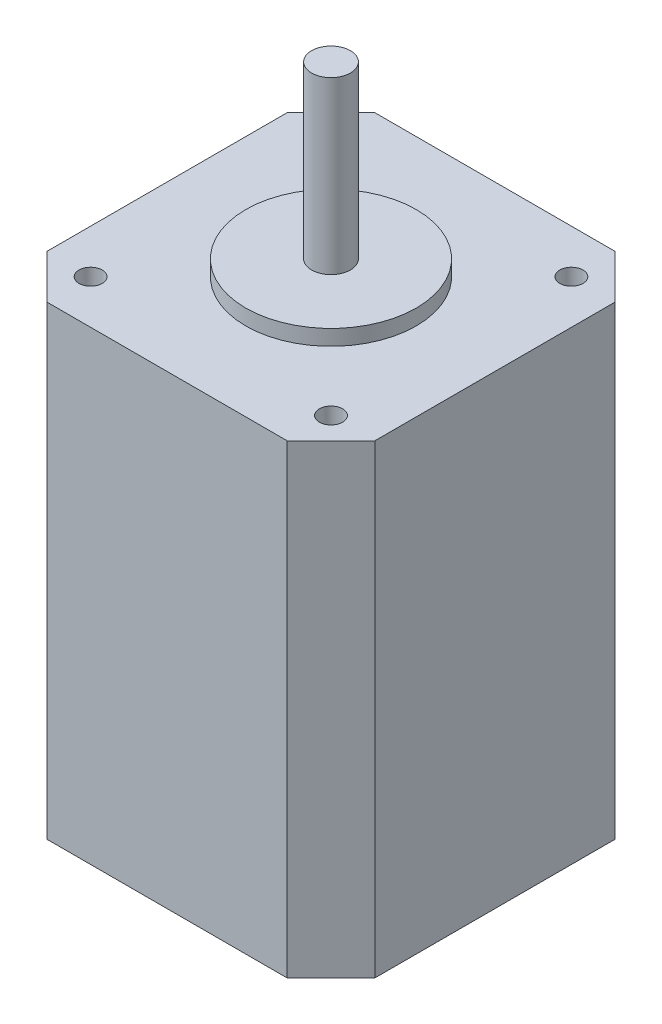
SolidWorks part; units mm, degrees
ref_plane "前基準面" through (0, 0, 0) normal (0, 0, 1) x (1, 0, 0)
ref_plane "上基準面" through (0, 0, 0) normal (0, 1, 0) x (1, 0, 0)
ref_plane "右基準面" through (0, 0, 0) normal (1, 0, 0) x (0, 0, -1)
sketch "草圖1" plane through (0, 0, 0) normal (0, 1, 0) x (1, 0, 0)
  line L0 (-15.5, -21.15) -> (-15.5, 21.15) construction
  line L1 (-15.5, 21.15) -> (15.5, 21.15)
  line L2 (-21.15, 15.5) -> (-21.15, -15.5)
  line L3 (-15.5, -21.15) -> (15.5, -21.15)
  line L4 (21.15, 15.5) -> (21.15, -15.5)
  line L5 (0, -21.15) -> (0, 21.15) construction
  line L6 (-21.15, 0) -> (21.15, 0) construction
  line L7 (15.5, -21.15) -> (15.5, 21.15) construction
  line L8 (-21.15, 15.5) -> (21.15, 15.5) construction
  line L9 (-21.15, -15.5) -> (21.15, -15.5) construction
  line L10 (-15.5, -21.15) -> (-21.15, -15.5)
  line L11 (15.5, -21.15) -> (21.15, -15.5)
  line L12 (-21.15, 15.5) -> (-15.5, 21.15)
  line L13 (15.5, 21.15) -> (21.15, 15.5)
  circle A0 centre (-15.5, 15.5) radius 1.5
  circle A1 centre (15.5, 15.5) radius 1.5
  circle A2 centre (15.5, -15.5) radius 1.5
  circle A3 centre (-15.5, -15.5) radius 1.5
  point P0 (0, 0)
  point P1 (-15.5, -15.5)
  point P2 (0, 0)
  point P3 (-15.5, 21.15)
  point P8 (-21.15, 15.5)
  point P23 (-21.15, 15.5)
  point P24 (-21.15, -15.5)
  point P25 (-15.5, -21.15)
  point P26 (15.5, -21.15)
  point P27 (0, 0)
  dimension "D3" = 3
  dimension "D1" = 42.3
  dimension "D2" = 42.3
  dimension "D4" = 31
  dimension "D5" = 31
  dimension "D6" = 45
  dimension "D7" = 225
  dimension "D8" = 135
extrude "填料-伸長1" add sketch "草圖1" along normal blind 60
sketch "草圖2" plane through (0, 60, 0) normal (0, 1, 0) x (1, 0, 0)
  circle A0 centre (0, 0) radius 11
  dimension "D1" = 22
extrude "填料-伸長2" add sketch "草圖2" along normal blind 2
sketch "草圖3" plane through (0, 62, 0) normal (0, 1, 0) x (1, 0, 0)
  circle A0 centre (0, 0) radius 2.5
  dimension "D1" = 5
extrude "填料-伸長3" add sketch "草圖3" along normal blind 22
